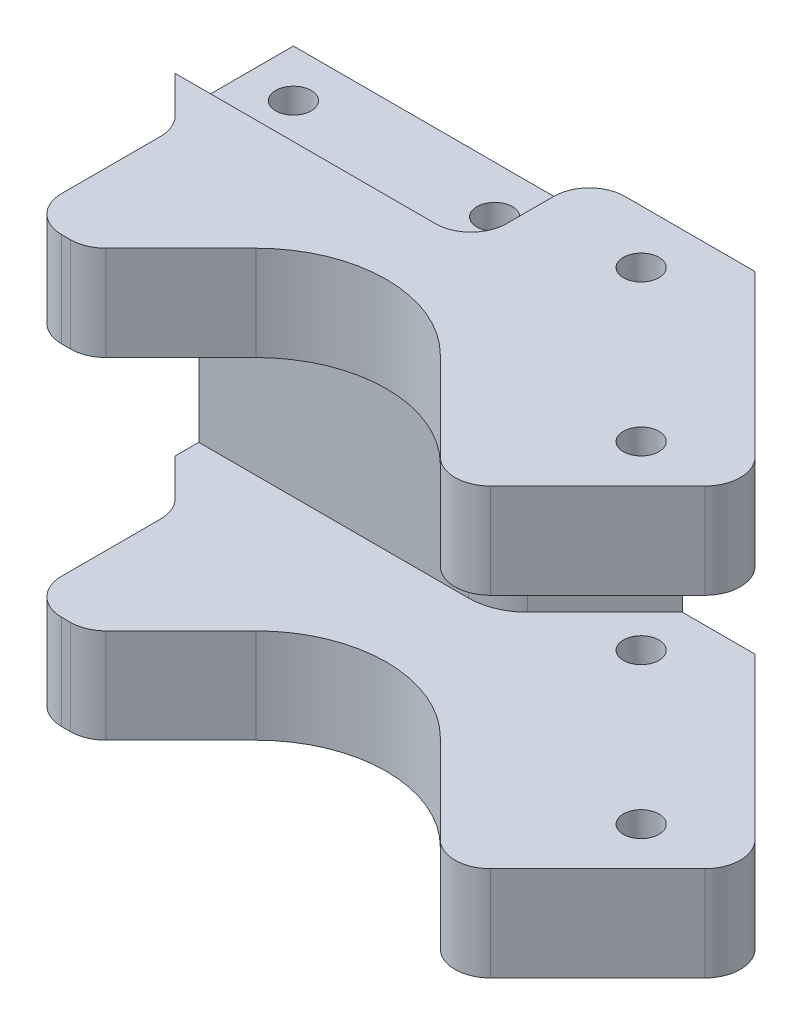
SolidWorks part; units mm, degrees
ref_plane "Front Plane" through (0, 0, 0) normal (0, 0, 1) x (1, 0, 0)
ref_plane "Top Plane" through (0, 0, 0) normal (0, 1, 0) x (1, 0, 0)
ref_plane "Right Plane" through (0, 0, 0) normal (1, 0, 0) x (0, 0, -1)
sketch "Sketch3" plane through (0, 5.4967, 0) normal (0, -1, 0) x (1, 0, 0)
  line L8 (-43.5722, -214.6789) -> (-43.5722, 19.4919) construction
  line L9 (-58.5723, 18.9356) -> (-63.5723, 18.9356)
  line L12 (-35.7941, 11.7137) -> (-26.1725, 21.3353)
  line L13 (-58.5723, 18.9356) -> (-51.3504, 11.7137)
  line L14 (-26.1725, 21.3353) -> (-12.8767, 8.0395)
  line L16 (-28.5722, -7.6561) -> (-12.8767, 8.0395)
  line L17 (-67.5734, -7.6561) -> (-28.5722, -7.6561)
  line L18 (-63.5723, 18.9356) -> (-63.5723, 6.345)
  line L19 (-43.5722, 19.4919) -> (-32.5722, 19.4919) construction
  line L21 (-67.5734, -7.6561) -> (-67.5734, 2.3439)
  line L22 (-67.5734, 2.3439) -> (-63.5723, 6.345)
  circle A0 centre (-43.5722, 19.4919) radius 11 construction
  arc A2 (-51.3504, 11.7137) -> (-35.7941, 11.7137) centre (-43.5722, 19.4919) ccw
  circle A4 centre (-33.6728, -3.1355) radius 1.5
  circle A5 centre (-20.9448, 9.5924) radius 1.5
  dimension "D1" = 135
extrude "Boss-Extrude1" add sketch "Sketch3" along normal blind 8
sketch "Sketch4" plane through (0, 25.4967, 0) normal (0, 1, 0) x (1, 0, 0)
  line L39 (-63.5723, -6.345) -> (-63.5723, -18.9356)
  line L40 (-67.5734, -2.3439) -> (-63.5723, -6.345)
  line L41 (-67.5734, 7.6561) -> (-67.5734, -2.3439)
  line L44 (-28.5722, 7.6561) -> (-67.5734, 7.6561)
  line L45 (-12.8767, -8.0395) -> (-28.5722, 7.6561)
  line L46 (-26.1725, -21.3353) -> (-12.8767, -8.0395)
  line L47 (-35.7941, -11.7137) -> (-26.1725, -21.3353)
  line L48 (-58.5723, -18.9356) -> (-51.3504, -11.7137)
  line L49 (-63.5723, -18.9356) -> (-58.5723, -18.9356)
  line L50 (-63.5723, -6.345) -> (-63.5723, -18.9356)
  line L51 (-67.5734, -2.3439) -> (-63.5723, -6.345)
  line L52 (-67.5734, 7.6561) -> (-67.5734, -2.3439)
  line L53 (-28.5722, 7.6561) -> (-67.5734, 7.6561)
  line L54 (-12.8767, -8.0395) -> (-28.5722, 7.6561)
  line L55 (-26.1725, -21.3353) -> (-12.8767, -8.0395)
  line L56 (-35.7941, -11.7137) -> (-26.1725, -21.3353)
  line L57 (-58.5723, -18.9356) -> (-51.3504, -11.7137)
  line L58 (-63.5723, -18.9356) -> (-58.5723, -18.9356)
  arc A5 (-35.7941, -11.7137) -> (-51.3504, -11.7137) centre (-43.5722, -19.4919) ccw
  arc A6 (-35.7941, -11.7137) -> (-51.3504, -11.7137) centre (-43.5722, -19.4919) ccw
  dimension "D1" = 0
extrude "Boss-Extrude2" add sketch "Sketch4" along normal blind 8
sketch "Sketch9" plane through (0, 25.4967, 0) normal (0, -1, 0) x (1, 0, 0)
  line L0 (-34.7096, -7.6561) -> (-42.7096, 0.3439)
  line L1 (-67.5734, -7.6561) -> (-28.5722, -7.6561) construction
  line L2 (-42.7096, 0.3439) -> (-67.5734, 0.3439)
  line L3 (-34.7096, -7.6561) -> (-67.5734, -7.6561)
  line L4 (-67.5734, -7.6561) -> (-67.5734, 0.3439)
  line L5 (-67.5734, 2.3439) -> (-67.5734, -7.6561) construction
  line L6 (-67.5734, -7.6561) -> (-28.5722, -7.6561) construction
  line L7 (-20.9448, 9.5924) -> (-33.6728, -3.1355) construction
extrude "Boss-Extrude3" add sketch "Sketch9" along normal blind 20
fillet "Fillet8" radius 3 5 edges at (-63.5723, 1.4967, 6.345) (-63.5723, 1.4967, 18.9356) (-58.5723, 1.4967, 18.9356) (-26.1725, 1.4967, 21.3353) (-12.8767, 1.4967, 8.0395)
fillet "Fillet9" radius 3 5 edges at (-12.8767, 29.4967, 8.0395) (-26.1725, 29.4967, 21.3353) (-58.5723, 29.4967, 18.9356) (-63.5723, 29.4967, 18.9356) (-63.5723, 29.4967, 6.345)
sketch "Sketch15" plane through (0, -2.5033, 0) normal (0, -1, 0) x (1, 0, 0)
  line L0 (-67.5734, -7.6561) -> (-28.5722, -7.6561) construction
  line L1 (-67.5734, 2.3439) -> (-42.5734, 2.3439)
  line L2 (-67.5734, 2.3439) -> (-67.5734, -7.6561)
  line L3 (-67.5734, -7.6561) -> (-42.5734, -7.6561)
  line L4 (-42.5734, 2.3439) -> (-42.5734, -7.6561)
extrude "Cut-Extrude3" cut sketch "Sketch15" against normal blind 3
sketch "Sketch17" plane through (0, 33.4967, 0) normal (0, 1, 0) x (1, 0, 0)
  line L4 (-67.5734, 7.6561) -> (-67.5734, -2.3439)
  line L5 (-42.5734, 7.6561) -> (-67.5734, 7.6561)
  line L6 (-42.5734, -2.3439) -> (-42.5734, 7.6561)
  line L7 (-67.5734, -2.3439) -> (-42.5734, -2.3439)
  line L9 (-42.5734, 7.6561) -> (-67.5734, 7.6561)
  line L10 (-42.5734, -2.3439) -> (-42.5734, 7.6561)
  line L11 (-67.5734, -2.3439) -> (-42.5734, -2.3439)
  line L13 (-67.5734, 7.6561) -> (-67.5734, -2.3439)
  dimension "D1" = 0
extrude "Cut-Extrude4" cut sketch "Sketch17" against normal blind 3
fillet "Fillet4" radius 3 4 edges at (-42.5734, 31.9967, 2.3439) (-42.5734, 31.9967, -7.6561) (-42.5734, -1.0033, 2.3439) (-42.5734, -1.0033, -7.6561)
sketch "Sketch18" plane through (0, -2.5033, 0) normal (0, -1, 0) x (1, 0, 0)
  circle A0 centre (-46.5734, -3.6561) radius 1.5
  circle A1 centre (-63.5734, -3.6561) radius 1.5
extrude "Cut-Extrude5" cut sketch "Sketch18" against normal up to surface (36 mm away) up to face at (-44.7247, 33.4967, 8.0732)
fillet "Fillet7" radius 5 1 edges at (-42.7096, 15.4967, 0.3439)
sketch "Sketch19" plane through (0, 25.4967, 0) normal (0, -1, 0) x (1, 0, 0)
  circle A0 centre (-33.6728, -3.1355) radius 1.5 construction
  circle A1 centre (-20.9448, 9.5924) radius 1.5 construction
  circle A2 centre (-33.6728, -3.1355) radius 1.5
  circle A3 centre (-20.9448, 9.5924) radius 1.5
extrude "Cut-Extrude6" cut sketch "Sketch19" against normal up to surface (8 mm away) up to face at (-44.7247, 33.4967, 8.0732)
